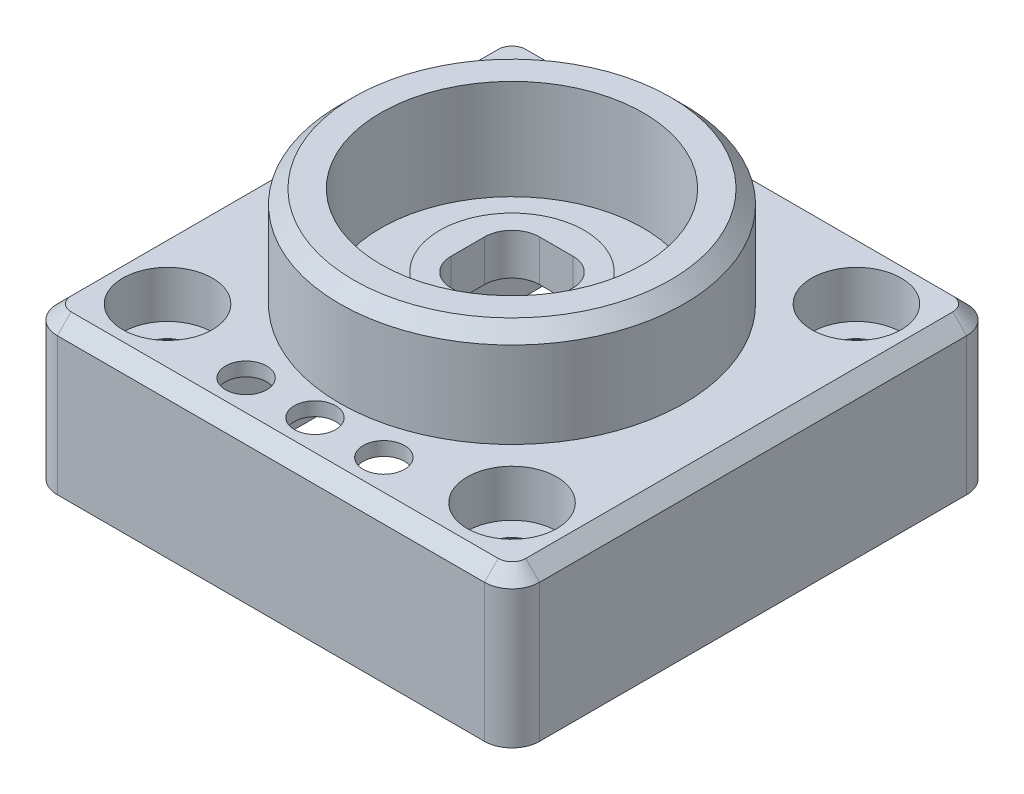
SolidWorks part; units mm, degrees
material "3.1355 (EN-AW 2024)"
ref_plane "Спереди" through (0, 0, 0) normal (0, 0, 1) x (1, 0, 0)
ref_plane "Сверху" through (0, 0, 0) normal (0, 1, 0) x (1, 0, 0)
ref_plane "Справа" through (0, 0, 0) normal (1, 0, 0) x (0, 0, -1)
sketch "Эскиз1" plane through (0, 0, 0) normal (0, 1, 0) x (1, 0, 0)
  circle A0 centre (0, 0) radius 12.5
  circle A1 centre (0, 0) radius 9.53
  dimension "D1" = 25
  dimension "D2" = 19.06
extrude "Основание" add sketch "Эскиз1" against normal blind 7.25
sketch "Эскиз8" plane through (0, -7.25, 0) normal (0, -1, 0) x (1, 0, 0)
  line L1 (-15.5, 17.5) -> (15.5, 17.5)
  line L2 (-17.5, 15.5) -> (-17.5, -15.5)
  line L3 (-15.5, -17.5) -> (15.5, -17.5)
  line L4 (17.5, 15.5) -> (17.5, -15.5)
  arc A0 (-17.5, -15.5) -> (-15.5, -17.5) centre (-15.5, -15.5) ccw
  arc A1 (15.5, -17.5) -> (17.5, -15.5) centre (15.5, -15.5) ccw
  arc A2 (15.5, 17.5) -> (17.5, 15.5) centre (15.5, 15.5) cw
  arc A3 (-15.5, 17.5) -> (-17.5, 15.5) centre (-15.5, 15.5) ccw
  point P4 (-17.5, 0)
  point P7 (0, 17.5)
  dimension "D2" = 2
  dimension "D1" = 17.5
extrude "Основание квадрат" add sketch "Эскиз8" along normal blind 11
sketch "Эскиз9" plane through (0, -18.25, 0) normal (0, -1, 0) x (1, 0, 0)
  line L1 (-6.5, 16) -> (6.5, 16)
  line L2 (-8.5, 14) -> (-8.5, -14)
  line L3 (-6.5, -16) -> (6.5, -16)
  line L4 (8.5, 14) -> (8.5, -14)
  arc A0 (-8.5, -14) -> (-6.5, -16) centre (-6.5, -14) ccw
  arc A1 (6.5, -16) -> (8.5, -14) centre (6.5, -14) ccw
  arc A2 (6.5, 16) -> (8.5, 14) centre (6.5, 14) cw
  arc A3 (-6.5, 16) -> (-8.5, 14) centre (-6.5, 14) ccw
  point P4 (-8.5, 0)
  point P6 (0, 16)
  point P9 (-8.5, -16)
  point P14 (8.5, 16)
  point P17 (-8.5, 16)
  dimension "D3" = 2
  dimension "D1" = 32
  dimension "D2" = 17
extrude "Вырез платы" cut sketch "Эскиз9" against normal blind 10
sketch "Эскиз30" plane through (0, -8.25, 0) normal (0, -1, 0) x (-1, 0, 0)
  line L0 (0, -16.5) -> (0, 0) construction
hole_wizard "Крепление модуля М3" positions "Эскиз12" profile "Эскиз10" counterbore size "M3" standard "ISO" end condition up to next
sketch "Эскиз12" plane through (0, -7.25, 0) normal (0, 1, 0) x (1, 0, 0)
  line L0 (-12.5, 12.5) -> (-12.5, 17.5) construction
  line L1 (-15.5, 17.5) -> (15.5, 17.5) construction
  line L4 (-12.5, 12.5) -> (-17.5, 12.5) construction
  line L5 (-17.5, -15.5) -> (-17.5, 15.5) construction
  line L8 (12.5, 12.5) -> (17.5, 12.5) construction
  line L9 (17.5, 15.5) -> (17.5, -15.5) construction
  line L12 (-12.5, -12.5) -> (-12.5, -17.5) construction
  line L13 (15.5, -17.5) -> (-15.5, -17.5) construction
  point P0 (-12.5, 12.5)
  point P2 (12.5, 12.5)
  point P4 (12.5, -12.5)
  point P6 (-12.5, -12.5)
  dimension "D1" = 5
sketch "Эскиз10" plane through (-12.5, -7.25, -12.5) normal (1, 0, 0) x (0, 0, 1)
  line L0 (0, 0) -> (0, 11)
  line L1 (0, 11) -> (1.7, 11)
  line L2 (1.7, 3.425) -> (1.7, 11)
  line L3 (1.7, 3.425) -> (1.725, 3.4)
  line L4 (1.725, 3.4) -> (3.25, 3.4)
  line L5 (3.25, 3.4) -> (3.25, 0)
  line L7 (0, 0) -> (3.25, 0)
  line L9 (-1.7, 3.425) -> (-1.725, 3.4) construction
  line L11 (0, -6.35) -> (0, 107.95) construction
  dimension "Диаметр сквозного отверстия" = 3.4
  dimension "Thru Hole Depth" = 11
  dimension "Диаметр цековки" = 6.5
  dimension "Глубина цековки" = 3.4
  dimension "Диаметр средней зенковки" = 3.45
  dimension "Угол средней зенковки" = 90
hole_wizard "Светодиоды" positions "Эскиз16" profile "Эскиз15" hole size "Ø3.0" standard "ISO" end condition through all
sketch "Эскиз16" plane through (0, -7.25, 0) normal (0, 1, 0) x (1, 0, 0)
  line L0 (-5, -14.3) -> (0, -14.3) construction
  line L1 (0, -14.3) -> (5, -14.3) construction
  point P0 (0, -14.3)
  point P2 (-5, -14.3)
  point P4 (5, -14.3)
  dimension "D1" = 5
  dimension "D2" = 14.3
sketch "Эскиз15" plane through (0, -7.25, 14.3) normal (1, 0, 0) x (0, 0, 1)
  line L0 (0, 0) -> (0, 11)
  line L1 (0, 11) -> (1.5, 11)
  line L2 (1.5, 11) -> (1.5, 0)
  line L5 (1.5, 0) -> (0, 0)
  line L11 (0, -6.35) -> (0, 107.95) construction
  dimension "Диаметр сквозного отверстия" = 3
  dimension "Глубина сквозного отверстия" = 11
sketch "Эскиз29" plane through (0, -8.25, 0) normal (0, -1, 0) x (1, 0, 0)
  line L0 (-6.5, 6.5) -> (0, 6.5) construction
  line L1 (-6.5, -6.5) -> (0, -6.5) construction
  line L2 (0, 200016.5) -> (0, -200000) construction
  line L3 (6.5, -6.5) -> (0, -6.5) construction
  line L5 (0, 6.5) -> (6.5, 6.5) construction
  line L6 (-6.5, -5) -> (-8.5, -5)
  line L7 (-8.5, 14) -> (-8.5, -14) construction
  line L8 (-8.5, -5) -> (-8.5, -8)
  line L9 (-8.5, -8) -> (-6.5, -8)
  line L10 (6.5, -5) -> (8.5, -5)
  line L11 (8.5, -14) -> (8.5, 14) construction
  line L12 (8.5, -5) -> (8.5, -8)
  line L13 (8.5, -14) -> (8.5, 14) construction
  line L14 (8.5, -8) -> (6.5, -8)
  line L15 (0, -6.5) -> (0, 0) construction
  line L16 (0, 0) -> (0, 6.5) construction
  line L17 (-6.5, 8) -> (-8.5, 8)
  line L18 (-8.5, 8) -> (-8.5, 5)
  line L19 (-8.5, 5) -> (-6.5, 5)
  line L20 (6.5, 8) -> (8.5, 8)
  line L21 (8.5, 8) -> (8.5, 5)
  line L22 (8.5, 5) -> (6.5, 5)
  arc A3 (-6.5, 5) -> (-6.5, 8) centre (-6.5, 6.5) ccw
  arc A4 (6.5, 8) -> (6.5, 5) centre (6.5, 6.5) ccw
  arc A5 (-6.5, -8) -> (-6.5, -5) centre (-6.5, -6.5) ccw
  arc A6 (6.5, -5) -> (6.5, -8) centre (6.5, -6.5) ccw
  point P28 (0, -6.5)
  dimension "D1" = 1.5
  dimension "D5" = 6.5
extrude "Вынос платы" add sketch "Эскиз29" along normal blind 1.6
hole_wizard "Крепление платы M2" positions "Эскиз34" profile "Эскиз35" tap size "M2" standard "ISO"
sketch "Эскиз34" plane through (0, -9.85, 0) normal (0, -1, 0) x (-1, 0, 0)
  circle A1 centre (6.5, -6.5) radius 1.5 construction
  circle A2 centre (-6.5, -6.5) radius 1.5 construction
  arc A3 (6.5, 8) -> (6.5, 5) centre (6.5, 6.5) ccw construction
  arc A4 (-6.5, 5) -> (-6.5, 8) centre (-6.5, 6.5) ccw construction
  point P0 (6.5, -6.5)
  point P2 (-6.5, -6.5)
  point P11 (6.5, 6.5)
  point P13 (-6.5, 6.5)
cosmetic thread "Отверстие резьбы7" parameters "D1"=2, "D2"=2
cosmetic thread "Отверстие резьбы8" parameters "D1"=2, "D2"=2
cosmetic thread "Отверстие резьбы9" parameters "D1"=2, "D2"=2
cosmetic thread "Отверстие резьбы10" parameters "D1"=2, "D2"=2
sketch "Эскиз35" plane through (-6.5, -9.85, 6.5) normal (1, 0, 0) x (0, 0, -1)
  line L0 (0, 0) -> (0, 2.4807)
  line L1 (0, 2.4807) -> (0.8, 2)
  line L2 (0.8, 2) -> (0.8, 0)
  line L5 (0.8, 0) -> (0, 0)
  line L10 (0, 2.4807) -> (-0.8, 2) construction
  line L11 (0, -6.35) -> (0, 107.95) construction
  dimension "Диаметр сверла" = 1.6
  dimension "Глубина сверла" = 2
  dimension "Угол заточки сверла" = 118
sketch "Эскиз22" plane through (0, 0, -16) normal (0, 0, -1) x (-1, 0, 0)
  line L1 (6.5, -8.25) -> (-6.5, -8.25) construction
  line L6 (15.5, -18.25) -> (-15.5, -18.25) construction
  circle A0 centre (0, -13.95) radius 2.6
  point P4 (0, -18.25)
  point P7 (0, -8.25)
  dimension "D1" = 5.2
  dimension "D2" = 5.7
extrude "Вырез кабеля" cut sketch "Эскиз22" along normal through all
sketch "Эскиз26" plane through (0, -7.25, 0) normal (0, 1, 0) x (1, 0, 0)
  circle A0 centre (0, 0) radius 5.25
  dimension "D1" = 10.5
extrude "Для пружины" add sketch "Эскиз26" along normal blind 2
sketch "Эскиз25" plane through (0, -5.25, 0) normal (0, 1, 0) x (1, 0, 0)
  line L1 (-1.21, 3.21) -> (1.21, 3.21)
  line L2 (-3.21, 1.21) -> (-3.21, -1.21)
  line L3 (-1.21, -3.21) -> (1.21, -3.21)
  line L4 (3.21, 1.21) -> (3.21, -1.21)
  arc A1 (-3.21, -1.21) -> (-1.21, -3.21) centre (-1.21, -1.21) ccw
  arc A2 (1.21, -3.21) -> (3.21, -1.21) centre (1.21, -1.21) ccw
  arc A3 (1.21, 3.21) -> (3.21, 1.21) centre (1.21, 1.21) cw
  arc A4 (-1.21, 3.21) -> (-3.21, 1.21) centre (-1.21, 1.21) ccw
  point P0 (0, 0)
  point P1 (-3.21, 0)
  point P2 (3.21, 0)
  point P3 (0, 3.21)
  point P4 (0, -3.21)
  dimension "D1" = 2
  dimension "D2" = 6.42
extrude "Вырез щупа" cut sketch "Эскиз25" against normal through all
chamfer "Фаска 1" distance 1 angle 45 9 edges at (0, -7.25, 17.5) (-16.9142, -7.25, 16.9142) (16.9142, -7.25, 16.9142) (17.5, -7.25, 0) (16.9142, -7.25, -16.9142) (0, -7.25, -17.5) (-16.9142, -7.25, -16.9142) (-17.5, -7.25, 0) (0, 0, 12.5)
fillet "Скругление1" radius 4 8 edges at (8.5, -9.05, -8) (8.5, -9.05, 5) (8.5, -9.05, -5) (8.5, -9.05, 8) (-8.5, -9.05, 8) (-8.5, -9.05, 5) (-8.5, -9.05, -5) (-8.5, -9.05, -8)
sketch "Эскиз36" plane through (0, -18.25, 0) normal (0, -1, 0) x (1, 0, 0)
  line L1 (-14, 16) -> (14, 16)
  line L2 (-16, 14) -> (-16, -14)
  line L3 (-14, -16) -> (14, -16)
  line L4 (16, 14) -> (16, -14)
  line L5 (-16, 16) -> (16, -16) construction
  line L6 (-16, -16) -> (16, 16) construction
  arc A0 (-16, -14) -> (-14, -16) centre (-14, -14) ccw
  arc A1 (14, -16) -> (16, -14) centre (14, -14) ccw
  arc A2 (14, 16) -> (16, 14) centre (14, 14) cw
  arc A3 (-14, 16) -> (-16, 14) centre (-14, 14) ccw
  point P0 (0, 0)
  dimension "D2" = 2
  dimension "D1" = 32
extrude "Вырез Дна" cut sketch "Эскиз36" against normal blind 2.5
hole_wizard "Крепление крышки М3" positions "Эскиз37" profile "Эскиз39" tap size "M3" standard "DIN"
sketch "Эскиз37" plane through (0, -15.75, 0) normal (0, -1, 0) x (-1, 0, 0)
  line L0 (11.75, 0) -> (0, 0) construction
  line L1 (0, 0) -> (-11.75, 0) construction
  point P0 (11.75, 0)
  point P2 (-11.75, 0)
  dimension "D1" = 11.75
sketch "Эскиз39" plane through (-11.75, -15.75, 0) normal (1, 0, 0) x (0, 0, -1)
  line L0 (0, 0) -> (0, 7.7511)
  line L1 (0, 7.7511) -> (1.25, 7)
  line L2 (1.25, 7) -> (1.25, 0)
  line L5 (1.25, 0) -> (0, 0)
  line L10 (0, 7.7511) -> (-1.25, 7) construction
  line L11 (0, -6.35) -> (0, 107.95) construction
  dimension "Диаметр сверла" = 2.5
  dimension "Глубина сверла" = 7
  dimension "Угол заточки сверла" = 118
cosmetic thread "Отверстие резьбы13" parameters "D1"=6, "D2"=3
cosmetic thread "Отверстие резьбы14" parameters "D1"=6, "D2"=3
